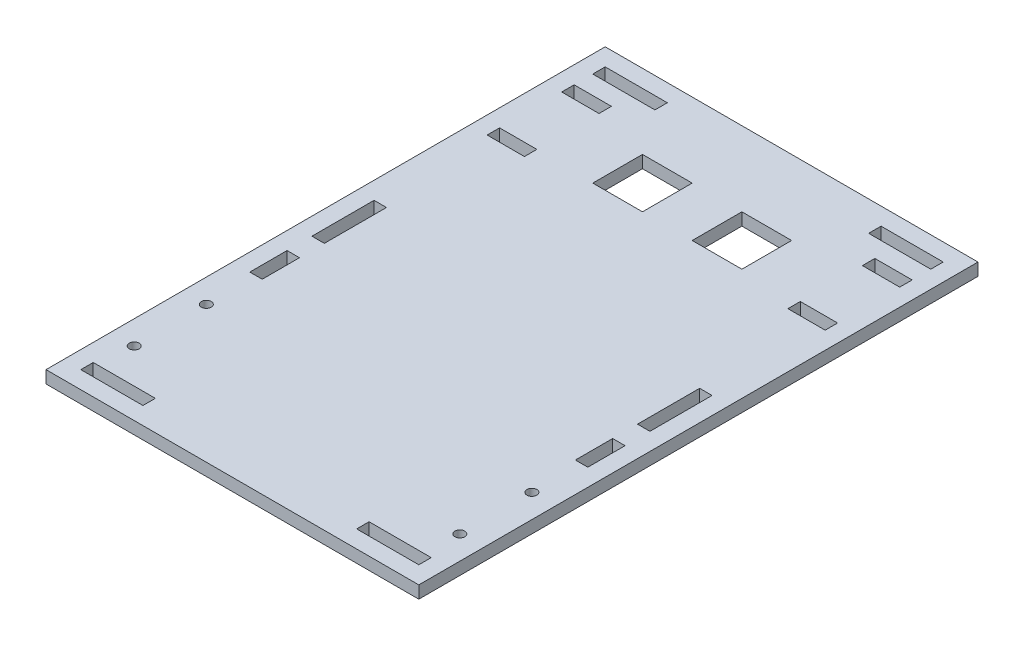
SolidWorks part; units mm, degrees
ref_plane "Front Plane" through (0, 0, 0) normal (0, 0, 1) x (1, 0, 0)
ref_plane "Top Plane" through (0, 0, 0) normal (0, 1, 0) x (1, 0, 0)
ref_plane "Right Plane" through (0, 0, 0) normal (1, 0, 0) x (0, 0, -1)
sketch "Sketch1" plane through (0, 0, 0) normal (0, 1, 0) x (1, 0, 0)
  line L1 (-75, 112.5) -> (75, 112.5)
  line L2 (-75, 112.5) -> (-75, -112.5)
  line L3 (-75, -112.5) -> (75, -112.5)
  line L4 (75, 112.5) -> (75, -112.5)
  point P4 (0, 112.5)
  point P6 (-75, 0)
  dimension "D1" = 150
  dimension "D2" = 225
extrude "Boss-Extrude1" add sketch "Sketch1" along normal blind 5
sketch "Sketch10" plane through (0, 5, 0) normal (0, 1, 0) x (1, 0, 0)
  line L0 (0, 0) -> (-75, 0) construction
  line L1 (-68, -105.5) -> (-43, -105.5)
  line L2 (-68, -105.5) -> (-68, -100.5)
  line L3 (-68, -100.5) -> (-43, -100.5)
  line L4 (-43, -105.5) -> (-43, -100.5)
  line L9 (-75, 112.5) -> (-75, -112.5) construction
  line L10 (0, 0) -> (0, -112.5) construction
  line L11 (-75, -112.5) -> (75, -112.5) construction
  line L12 (-68, 100.5) -> (-43, 100.5)
  line L13 (-43, 105.5) -> (-43, 100.5)
  line L14 (-68, 105.5) -> (-43, 105.5)
  line L15 (-68, 105.5) -> (-68, 100.5)
  line L16 (68, -100.5) -> (43, -100.5)
  line L17 (43, -105.5) -> (43, -100.5)
  line L18 (68, -105.5) -> (43, -105.5)
  line L19 (68, -105.5) -> (68, -100.5)
  line L20 (68, 105.5) -> (68, 100.5)
  line L21 (68, 105.5) -> (43, 105.5)
  line L22 (43, 105.5) -> (43, 100.5)
  line L23 (68, 100.5) -> (43, 100.5)
  line L24 (68, -12.5) -> (63, -12.5)
  line L25 (-68, 12.5) -> (-63, 12.5)
  line L26 (-68, 12.5) -> (-68, -12.5)
  line L27 (-68, -12.5) -> (-63, -12.5)
  line L28 (-63, 12.5) -> (-63, -12.5)
  line L29 (63, 12.5) -> (63, -12.5)
  line L30 (68, 12.5) -> (63, 12.5)
  line L31 (68, 12.5) -> (68, -12.5)
  point P29 (-68, 0)
  dimension "D1" = 7
  dimension "D2" = 7
  dimension "D3" = 5
  dimension "D4" = 25
extrude "Cut-Extrude5" cut sketch "Sketch10" against normal up to surface (5 mm away) up to face at (0, 0, 0)
sketch "Sketch11" plane through (0, 5, 0) normal (0, 1, 0) x (1, 0, 0)
  line L0 (-68, 105.5) -> (-68, 100.5) construction
  line L1 (-68, 93) -> (-53, 93)
  line L2 (-68, 93) -> (-68, 88)
  line L3 (-68, 88) -> (-53, 88)
  line L4 (-53, 93) -> (-53, 88)
  line L5 (0, 0) -> (0, 112.5) construction
  line L6 (75, 112.5) -> (-75, 112.5) construction
  line L7 (68, 88) -> (53, 88)
  line L8 (53, 93) -> (53, 88)
  line L9 (68, 93) -> (53, 93)
  line L10 (68, 93) -> (68, 88)
  line L11 (-68, 58) -> (-53, 58)
  line L12 (-68, 58) -> (-68, 63)
  line L13 (-68, 63) -> (-53, 63)
  line L14 (-53, 58) -> (-53, 63)
  line L15 (68, 58) -> (68, 63)
  line L16 (68, 63) -> (53, 63)
  line L17 (53, 58) -> (53, 63)
  line L18 (68, 58) -> (53, 58)
  dimension "D1" = 7.5
  dimension "D2" = 5
  dimension "D3" = 15
  dimension "D4" = 25
  dimension "D5" = 15
  dimension "D6" = 5
extrude "Cut-Extrude6" cut sketch "Sketch11" against normal up to surface (5 mm away) up to face at (-65.5, 0, 0)
sketch "Sketch12" plane through (0, 5, 0) normal (0, 1, 0) x (1, 0, 0)
  line L0 (0, 0) -> (0, -112.5) construction
  line L1 (-75, -112.5) -> (75, -112.5) construction
  line L2 (-68, 12.5) -> (-68, -12.5) construction
  line L3 (-68, -22.5) -> (-63, -22.5)
  line L4 (-68, -22.5) -> (-68, -37.5)
  line L5 (-68, -37.5) -> (-63, -37.5)
  line L6 (-63, -22.5) -> (-63, -37.5)
  line L7 (68, -37.5) -> (63, -37.5)
  line L8 (63, -22.5) -> (63, -37.5)
  line L9 (68, -22.5) -> (63, -22.5)
  line L10 (68, -22.5) -> (68, -37.5)
  dimension "D1" = 5
  dimension "D2" = 15
  dimension "D3" = 10
extrude "Cut-Extrude7" cut sketch "Sketch12" against normal up to surface (5 mm away) up to face at (60.5, 0, -90.5)
sketch "Sketch13" plane through (0, 5, 0) normal (0, 1, 0) x (1, 0, 0)
  line L0 (0, 0) -> (0, -112.5) construction
  line L1 (-75, -112.5) -> (75, -112.5) construction
  line L13 (-68, -37.5) -> (-63, -37.5) construction
  circle A0 centre (-65.5, -57.5) radius 2
  circle A1 centre (-65.5, -86.5) radius 2
  circle A2 centre (65.5, -86.5) radius 2
  circle A3 centre (65.5, -57.5) radius 2
  point P9 (-64.9811, -86.3921)
  point P10 (-58.8913, -57.0982)
  point P11 (0, 0)
  point P15 (-65.5, -37.5)
  dimension "D1" = 4
  dimension "D2" = 29
  dimension "D3" = 20
extrude "Cut-Extrude8" cut sketch "Sketch13" against normal up to surface (5 mm away) up to face at (-65.5, 0, 30)
sketch "Sketch14" plane through (0, 5, 0) normal (0, 1, 0) x (1, 0, 0)
  line L0 (0, 112.5) -> (0, 0) construction
  line L1 (75, 112.5) -> (-75, 112.5) construction
  line L2 (30, 62.5) -> (10, 62.5)
  line L3 (-30, 82.5) -> (-10, 82.5)
  line L4 (-30, 82.5) -> (-30, 62.5)
  line L5 (-30, 62.5) -> (-10, 62.5)
  line L6 (-10, 82.5) -> (-10, 62.5)
  line L7 (10, 82.5) -> (10, 62.5)
  line L8 (30, 82.5) -> (10, 82.5)
  line L9 (30, 82.5) -> (30, 62.5)
  dimension "D1" = 20
  dimension "D2" = 45
  dimension "D3" = 20
  dimension "D4" = 30
extrude "Cut-Extrude9" cut sketch "Sketch14" against normal up to surface (5 mm away) up to face at (65.5, 0, 59.5)
